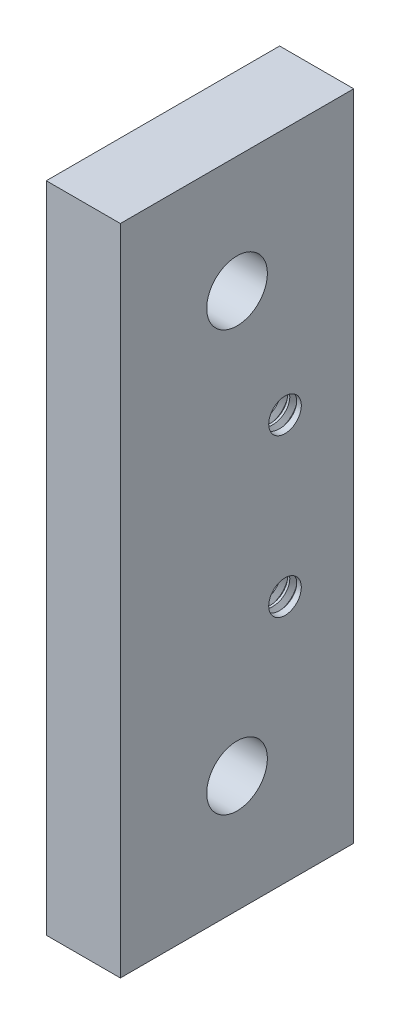
SolidWorks part; units mm, degrees
ref_plane "Front Plane" through (0, 0, 0) normal (0, 0, 1) x (1, 0, 0)
ref_plane "Top Plane" through (0, 0, 0) normal (0, 1, 0) x (1, 0, 0)
ref_plane "Right Plane" through (0, 0, 0) normal (1, 0, 0) x (0, 0, -1)
sketch "Sketch1" plane through (0, 0, 0) normal (1, 0, 0) x (0, 0, -1)
  line L0 (0, -18) -> (0, 18) construction
  line L1 (4.1101, 6.7469) -> (4.1101, -6.7469) construction
  line L2 (-10, 28) -> (10, 28)
  line L3 (-10, 28) -> (-10, -28)
  line L4 (-10, -28) -> (10, -28)
  line L5 (10, 28) -> (10, -28)
  line L6 (0, 0) -> (4.1101, 0) construction
  circle A0 centre (0, 18) radius 2.6
  circle A1 centre (0, -18) radius 2.6
  circle A2 centre (4.1101, 6.7469) radius 1.397
  circle A3 centre (4.1101, -6.7469) radius 1.397
  point P4 (0, 0)
  dimension "D1" = 5.2
  dimension "5.1" = 5.2
  dimension "D9" = 2.794
  dimension "D10" = 2.794
  dimension "D2" = 36
  dimension "D3" = 10
  dimension "D4" = 10
  dimension "D5" = 10
  dimension "D6" = 10
  dimension "D7" = 4.1101
  dimension "D8" = 13.4937
extrude "Boss-Extrude1" add sketch "Sketch1" along normal blind 3.175 and the other way blind 3.175
thread "Thread1" pitch 0.7937 method cut profile "Thread Profile1" start angle 0, offset 0, length 10, pitch 0.7937, diameter 2.794
ref_plane "Plane1" through (3.175, 6.7469, -2.7131) normal (0, -1, 0) x (0, 0, 1)
sketch "Thread Profile1" plane through (3.175, 6.7469, -2.7131) normal (0, -1, 0) x (0, 0, 1)
  line L0 (0, 0) -> (0, 0.7937) construction
  line L1 (0, 0) -> (0.4296, 0.248)
  line L2 (0.4296, 0.248) -> (0.4296, 0.3473)
  line L3 (0.4296, 0.3473) -> (0, 0.5953)
  line L4 (0.4296, 0.2977) -> (0, 0.2977) construction
  line L11 (0, 0) -> (0, 0.5953)
  point P2 (0, 0)
  dimension "Pitch" = 0.7937
  dimension "Profile_Angle" = 60
  dimension "Profile_Land" = 0.0992
  dimension "Profile_Height" = 0.4296
thread "Thread2" pitch 0.7937 method cut profile "Thread Profile2" start angle 0, offset 0, length 10, pitch 0.7937, diameter 2.794
ref_plane "Plane2" through (3.175, -6.7469, -2.7131) normal (0, -1, 0) x (0, 0, 1)
sketch "Thread Profile2" plane through (3.175, -6.7469, -2.7131) normal (0, -1, 0) x (0, 0, 1)
  line L0 (0, 0) -> (0, 0.7937) construction
  line L1 (0, 0) -> (0.4296, 0.248)
  line L2 (0.4296, 0.248) -> (0.4296, 0.3473)
  line L3 (0.4296, 0.3473) -> (0, 0.5953)
  line L4 (0.4296, 0.2977) -> (0, 0.2977) construction
  line L11 (0, 0) -> (0, 0.5953)
  point P2 (0, 0)
  dimension "Pitch" = 0.7937
  dimension "Profile_Angle" = 60
  dimension "Profile_Land" = 0.0992
  dimension "Profile_Height" = 0.4296
